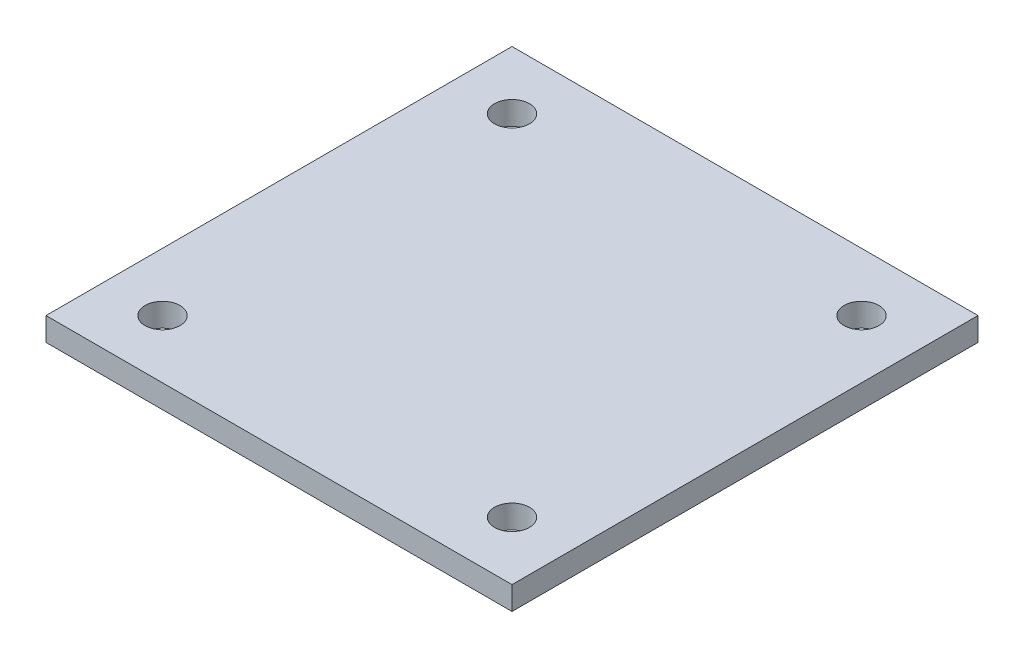
SolidWorks part; units mm, degrees
ref_plane "Front Plane" through (0, 0, 0) normal (0, 0, 1) x (1, 0, 0)
ref_plane "Top Plane" through (0, 0, 0) normal (0, 1, 0) x (1, 0, 0)
ref_plane "Right Plane" through (0, 0, 0) normal (1, 0, 0) x (0, 0, -1)
sketch "Sketch1" plane through (0, 0, 0) normal (0, 1, 0) x (1, 0, 0)
  line L1 (0, 0) -> (40, 0)
  line L2 (0, 0) -> (0, 40)
  line L3 (0, 40) -> (40, 40)
  line L4 (40, 0) -> (40, 40)
extrude "Boss-Extrude1" add sketch "Sketch1" along normal blind 2
sketch "Sketch2" plane through (0, 0, 0) normal (0, -1, 0) x (1, 0, 0)
  line L1 (40, 0) -> (35, 0) construction
  line L2 (40, 0) -> (40, -5) construction
  line L3 (40, -5) -> (35, -5) construction
  line L4 (35, 0) -> (35, -5) construction
  line L5 (0, -40) -> (5, -40) construction
  line L6 (0, -40) -> (0, -35) construction
  line L7 (0, -35) -> (5, -35) construction
  line L8 (5, -40) -> (5, -35) construction
  line L9 (35, -5) -> (5, -5) construction
  line L10 (35, -5) -> (35, -35) construction
  line L11 (35, -35) -> (5, -35) construction
  line L12 (5, -5) -> (5, -35) construction
  circle A0 centre (35, -5) radius 1.5
  circle A1 centre (35, -35) radius 1.5
  circle A2 centre (5, -5) radius 1.5
  circle A3 centre (5, -35) radius 1.5
extrude "Cut-Extrude1" cut sketch "Sketch2" against normal up to surface (2 mm away) up to face at (20, 2, -20)
sketch "Sketch3" plane through (0, 2, 0) normal (0, 1, 0) x (1, 0, 0)
  line L0 (40, 40) -> (0, 0) construction
  line L1 (40, 0) -> (0, 40) construction
ref_point "Point1"
ref_axis "CameraAxis" through (20, 2, -20) along (0, 1, 0)
ref_axis "Axis1" through (35, 2, -35) along (0, -1, 0)
ref_axis "Axis2" through (5, 2, -35) along (0, -1, 0)
ref_axis "Axis3" through (5, 2, -5) along (0, -1, 0)
ref_axis "Axis4" through (35, 2, -5) along (0, -1, 0)
ref_point "Point2"
ref_point "Point3"
sketch "Sketch4" plane through (0, 2, 0) normal (0, 1, 0) x (1, 0, 0)
  line L1 (5, 35) -> (35, 35)
  line L2 (5, 35) -> (5, 5)
  line L3 (5, 5) -> (35, 5)
  line L4 (35, 35) -> (35, 5)
  point P5 (35, 5)
  point P6 (35, 5)
